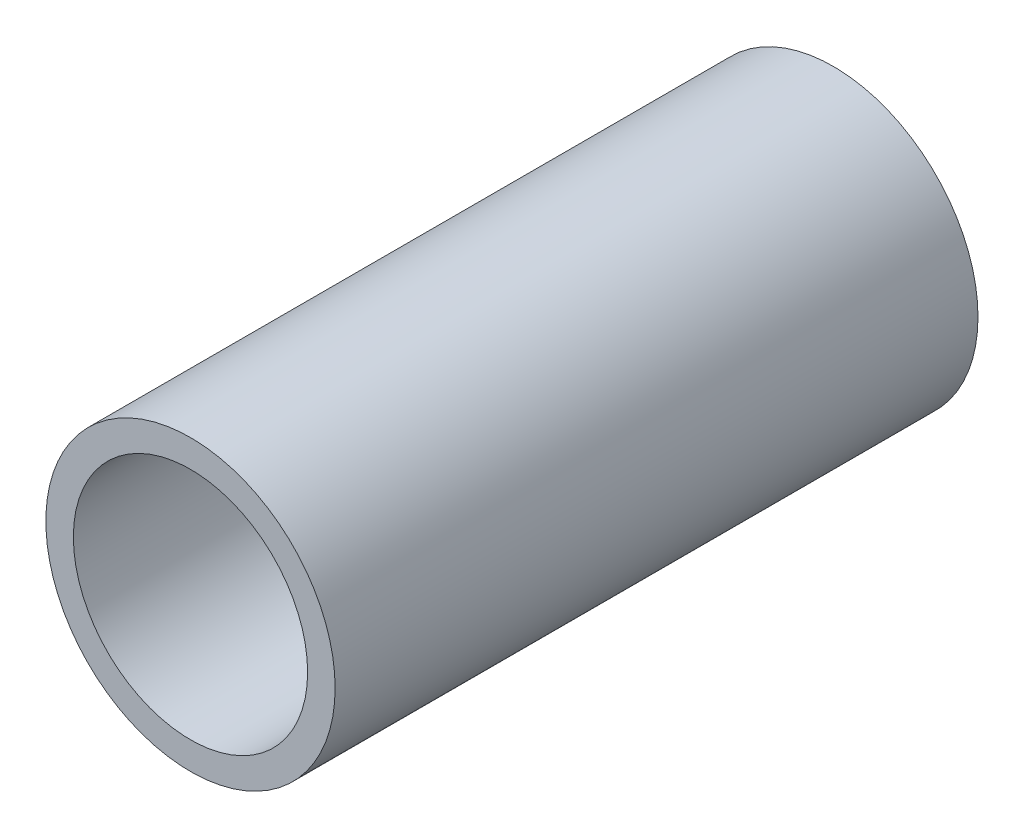
SolidWorks part; units mm, degrees
ref_plane "Front Plane" through (0, 0, 0) normal (0, 0, 1) x (1, 0, 0)
ref_plane "Top Plane" through (0, 0, 0) normal (0, 1, 0) x (1, 0, 0)
ref_plane "Right Plane" through (0, 0, 0) normal (1, 0, 0) x (0, 0, -1)
sketch "Sketch1" plane through (0, 0, 0) normal (0, 0, 1) x (1, 0, 0)
  circle A0 centre (0, 0) radius 18
extrude "Boss-Extrude1" add sketch "Sketch1" along normal blind 80
sketch "Sketch2" plane through (0, 0, 80) normal (0, 0, 1) x (1, 0, 0)
  circle A0 centre (0, 0) radius 14.576
extrude "Cut-Extrude1" cut sketch "Sketch2" against normal blind 60
sketch "Sketch3" plane through (0, 0, 0) normal (0, 0, -1) x (-1, 0, 0)
  circle A0 centre (0, 0) radius 4.3644
extrude "Cut-Extrude2" cut sketch "Sketch3" against normal blind 60
